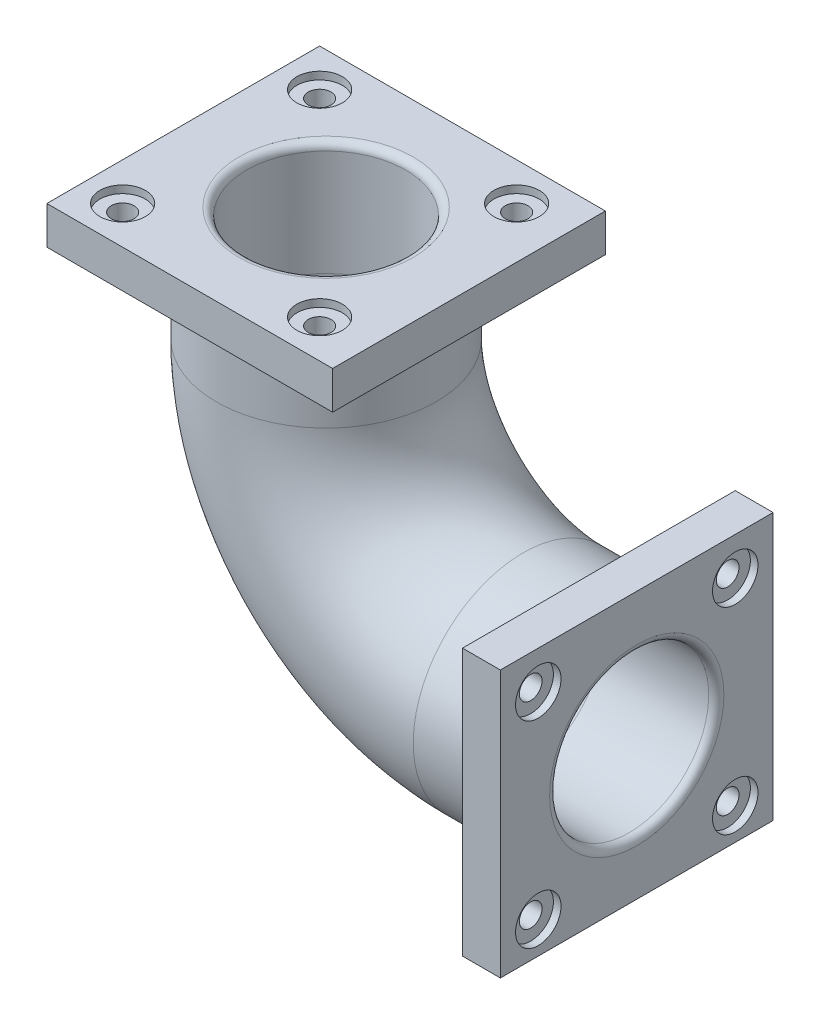
SolidWorks part; units mm, degrees
note: The reader was unsure of these and kept them because the rebuilt part matched: shared geometry of "Sketch12<3>", "Sketch20<3>".
ref_plane "Front Plane" through (0, 0, 0) normal (0, 0, 1) x (1, 0, 0)
ref_plane "Top Plane" through (0, 0, 0) normal (0, 1, 0) x (1, 0, 0)
ref_plane "Right Plane" through (0, 0, 0) normal (1, 0, 0) x (0, 0, -1)
sketch "Sketch1" plane through (0, 0, 0) normal (0, 0, 1) x (1, 0, 0)
  line L0 (-260, 0) -> (-260, 100)
  line L1 (0, -260) -> (100, -260)
  arc A0 (-260, 0) -> (0, -260) centre (0, 0) ccw
  point P1 (0, 0)
ref_plane "Plane1" through (100, 0, 0) normal (1, 0, 0) x (0, 0, -1)
sketch "Sketch9" plane through (100, 0, 0) normal (1, 0, 0) x (0, 0, -1)
  circle A0 centre (0, -260) radius 145
sweep "Sweep-Thin1" add profiles "Sketch9" path "Sketch1" parameters "D1"=40
ref_plane "Plane2" through (100, 0, 0) normal (1, 0, 0) x (0, 0, -1)
sketch "Sketch10" plane through (100, 0, 0) normal (1, 0, 0) x (0, 0, -1)
  line L0 (-253.6658, -125.3934) -> (315.1387, -125.3934) construction
  line L1 (-180, -436.0427) -> (180, -436.0427)
  line L2 (-180, -436.0427) -> (-180, -83.9573)
  line L3 (-180, -83.9573) -> (180, -83.9573)
  line L4 (180, -436.0427) -> (180, -83.9573)
  line L5 (315.1387, -379.0326) -> (-278.7786, -379.0326) construction
  line L6 (-120.5681, -23.6866) -> (-120.5681, -493.2957) construction
  line L7 (119.259, 20.2607) -> (119.259, -493.2957) construction
  point P0 (0, -260)
  dimension "D1" = 360
extrude "Boss-Extrude1" add sketch "Sketch10" along normal blind 50
sketch "Sketch12" plane through (150, 0, 0) normal (1, 0, 0) x (0, 0, -1)
  line L0 (-180, -83.9573) -> (180, -83.9573) construction
  line L3 (-180, -436.0427) -> (-180, -83.9573) construction
  circle A0 centre (-130, -133.9573) radius 30
  circle A1 centre (-130, -133.9573) radius 15
  circle A2 centre (130, -133.9573) radius 15
  circle A3 centre (130, -133.9573) radius 30
  circle A4 centre (130, -393.9573) radius 15
  circle A5 centre (130, -393.9573) radius 30
  circle A6 centre (-130, -393.9573) radius 15
  circle A7 centre (-130, -393.9573) radius 30
  circle A8 centre (0, -260) radius 105
  dimension "D3" = 2
  dimension "D1" = 50
  dimension "D2" = 50
  dimension "D4" = 2
extrude "Cut-Extrude3" cut sketch "Sketch12" against normal blind 50 contours A1 | A2 | A4 | A6 | A8
extrude "Cut-Extrude4" cut sketch "Sketch12<3>" against normal blind 10 contours A0
sketch "Sketch12<3>" plane through (150, 0, 0) normal (1, 0, 0) x (0, 0, -1) same geometry as "Sketch12"
ref_plane "Plane3" through (0, 100, 0) normal (0, 1, 0) x (1, 0, 0)
sketch "Sketch19" plane through (0, 100, 0) normal (0, 1, 0) x (1, 0, 0)
  line L1 (-71.4195, -180) -> (-448.5805, -180)
  line L2 (-71.4195, -180) -> (-71.4195, 180)
  line L3 (-71.4195, 180) -> (-448.5805, 180)
  line L4 (-448.5805, -180) -> (-448.5805, 180)
  line L5 (-71.4195, -180) -> (-448.5805, 180) construction
  line L6 (-71.4195, 180) -> (-448.5805, -180) construction
  point P0 (-260, 0)
extrude "Boss-Extrude2" add sketch "Sketch19" along normal blind 50
sketch "Sketch20" plane through (0, 150, 0) normal (0, 1, 0) x (1, 0, 0)
  line L0 (-448.5805, 180) -> (-448.5805, -180) construction
  line L2 (-448.5805, -180) -> (-71.4195, -180) construction
  circle A0 centre (-260, 0) radius 105
  circle A1 centre (-398.5805, -130) radius 30
  circle A2 centre (-398.5805, -130) radius 15
  circle A3 centre (-138.5805, -130) radius 15
  circle A4 centre (-138.5805, -130) radius 30
  circle A5 centre (-138.5805, 130) radius 15
  circle A6 centre (-138.5805, 130) radius 30
  circle A7 centre (-398.5805, 130) radius 15
  circle A8 centre (-398.5805, 130) radius 30
  dimension "D1" = 50
  dimension "D2" = 50
  dimension "D3" = 2
  dimension "D4" = 2
extrude "Cut-Extrude5" cut sketch "Sketch20" against normal blind 50 contours A0 | A2 | A7 | A5 | A3
extrude "Cut-Extrude6" cut sketch "Sketch20<3>" against normal blind 10 contours A4 A3 | A6 A5 | A8 A7 | A1 A2
sketch "Sketch20<3>" plane through (0, 150, 0) normal (0, 1, 0) x (1, 0, 0) same geometry as "Sketch20"
fillet "Fillet1" radius 10 2 edges at (-260, 150, 105) (150, -260, -105)
